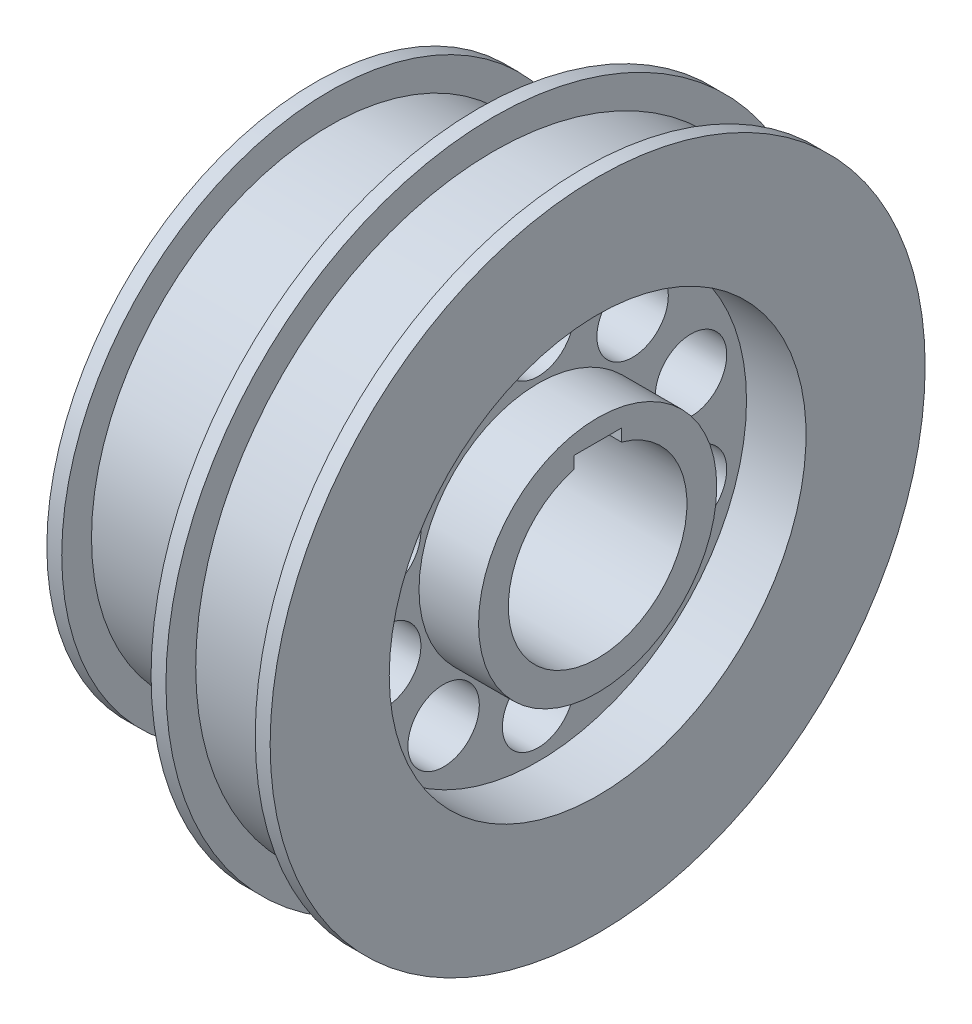
SolidWorks part; units mm, degrees
material "Plain Carbon Steel"
ref_plane "Front Plane" through (0, 0, 0) normal (0, 0, 1) x (1, 0, 0)
ref_plane "Top Plane" through (0, 0, 0) normal (0, 1, 0) x (1, 0, 0)
ref_plane "Right Plane" through (0, 0, 0) normal (1, 0, 0) x (0, 0, -1)
sketch "Sketch1" plane through (0, 0, 0) normal (1, 0, 0) x (0, 0, -1)
  line L2 (-4, 14.4568) -> (-4, 16.5)
  line L3 (-4, 16.5) -> (4, 16.5)
  line L4 (4, 14.4568) -> (4, 16.5)
  circle A0 centre (0, 0) radius 20
  circle A1 centre (0, 0) radius 45 construction
  circle A2 centre (0, 0) radius 60 construction
  arc A3 (-4, 14.4568) -> (4, 14.4568) centre (0, 0) ccw
  point P10 (0, 16.5)
  dimension "D1" = 40
  dimension "D2" = 90
  dimension "D3" = 120
  dimension "D4" = 30
  dimension "D5" = 8
  dimension "D6" = 16.5
extrude "Boss-Extrude1" add sketch "Sketch1" along normal blind 15 and the other way blind 15
sketch "Sketch2" plane through (-15, 0, 0) normal (-1, 0, 0) x (0, 0, 1)
  circle A0 centre (0, 0) radius 20
  circle A1 centre (0, 0) radius 6.5
  dimension "D1" = 40
  dimension "D2" = 13
extrude "Boss-Extrude2" add sketch "Sketch2" against normal blind 5
sketch "Sketch3" plane through (0, 0, 0) normal (1, 0, 0) x (0, 0, -1)
  circle A0 centre (0, 0) radius 40
  circle A2 centre (0, 27) radius 6
  circle A9 centre (0, 0) radius 17.5
  circle A10 centre (15.8702, 21.8435) radius 6
  circle A11 centre (25.6785, 8.3435) radius 6
  circle A12 centre (25.6785, -8.3435) radius 6
  circle A13 centre (15.8702, -21.8435) radius 6
  circle A14 centre (0, -27) radius 6
  circle A15 centre (-15.8702, -21.8435) radius 6
  circle A16 centre (-25.6785, -8.3435) radius 6
  circle A17 centre (-25.6785, 8.3435) radius 6
  circle A18 centre (-15.8702, 21.8435) radius 6
  point P19 (0, 0)
  point P28 (0, 0)
  dimension "D1" = 80
  dimension "D2" = 12
  dimension "D5" = 35
  dimension "D3" = 27
  dimension "D4" = 10
extrude "Boss-Extrude3" add sketch "Sketch3" along normal blind 5 and the other way blind 5
sketch "Sketch5" plane through (0, 0, 0) normal (0, 0, 1) x (1, 0, 0)
  line L1 (-32.5, 35) -> (-32.5, 45)
  line L2 (-5, 55) -> (-2.5, 55)
  line L3 (-2.5, 55) -> (-2.5, 50)
  line L4 (-2.5, 50) -> (12.5, 50)
  line L5 (12.5, 50) -> (12.5, 55)
  line L6 (12.5, 55) -> (15, 55)
  line L7 (15, 55) -> (15, 35)
  line L8 (-32.5, 45) -> (-30, 45)
  line L9 (15, 35) -> (-32.5, 35)
  line L10 (-30, 45) -> (-30, 40)
  line L11 (0, 0) -> (42.5827, 0) construction
  line L12 (-30, 40) -> (-5, 40)
  line L13 (-5, 40) -> (-5, 55)
  dimension "D1" = 55
  dimension "D2" = 50
  dimension "D3" = 35
  dimension "D4" = 2.5
  dimension "D5" = 15
  dimension "D6" = 5
  dimension "D7" = 25
  dimension "D8" = 2.5
  dimension "D9" = 40
  dimension "D10" = 5
revolve "Revolve1" add sketch "Sketch5" angle 360 about L11
fillet "Fillet1" radius 2.5 1 edges at (-15, 0, -20)
